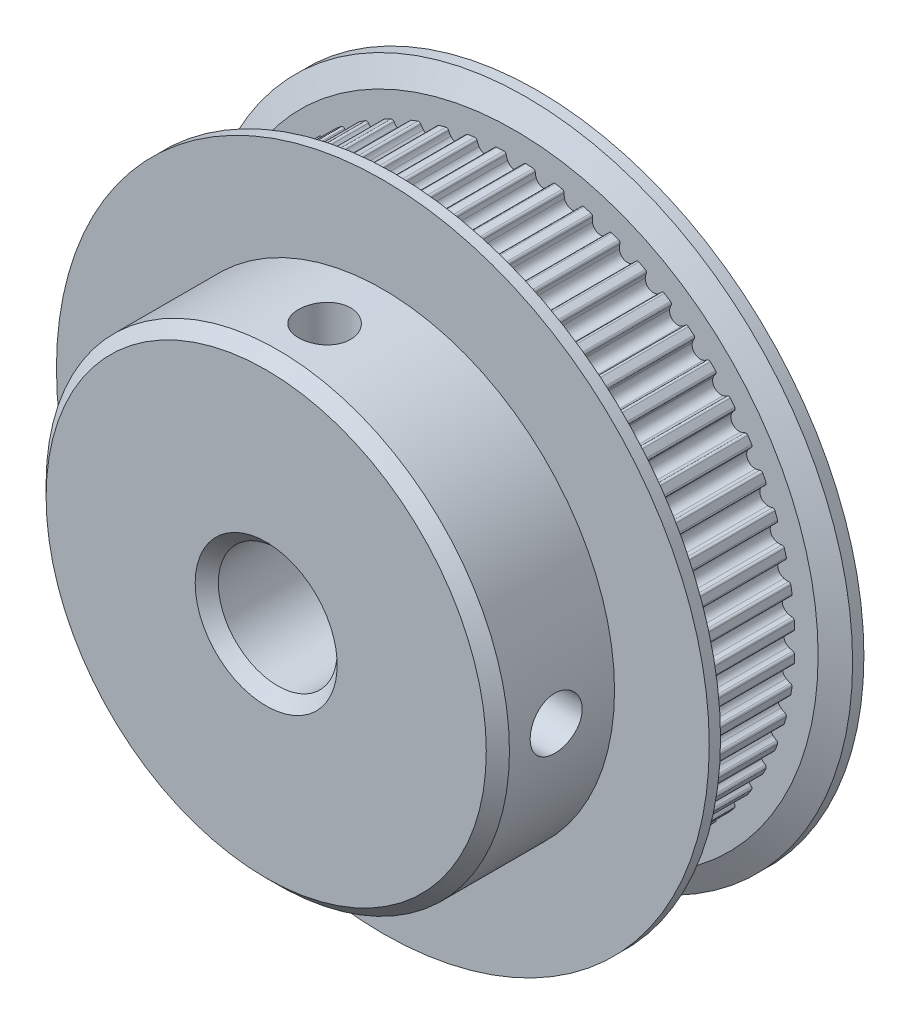
SolidWorks part; units mm, degrees
ref_plane "Front Plane" through (0, 0, 0) normal (0, 0, 1) x (1, 0, 0)
ref_plane "Top Plane" through (0, 0, 0) normal (0, 1, 0) x (1, 0, 0)
ref_plane "Right Plane" through (0, 0, 0) normal (1, 0, 0) x (0, 0, -1)
sketch "Sketch1" plane through (0, 0, 0) normal (0, 0, 1) x (1, 0, 0)
  line L1 (-1.9027, 18.097) -> (1.9027, 18.097) construction
  line L4 (0, 0) -> (0, 18.097) construction
  line L5 (0, 18.097) -> (0, 19.7034) construction
  line L6 (0, 19.101) -> (1.9973, 18.9963) construction
  line L7 (1.9973, 18.9963) -> (2.8966, 18.9017) construction
  line L8 (1.9973, 18.9963) -> (1.9027, 18.097) construction
  line L9 (-1.9973, 18.9963) -> (-1.9027, 18.097) construction
  line L10 (-1.9707, 18.7437) -> (-2.31, 21.971)
  line L11 (-2.31, 21.971) -> (2.31, 21.971)
  line L12 (2.31, 21.971) -> (1.9707, 18.7437)
  circle A0 centre (0, 0) radius 19.101 construction
  circle A1 centre (0, 0) radius 21.971 construction
  circle A2 centre (0, 0) radius 18.847 construction
  arc A3 (-0.4989, 18.4088) -> (0.4989, 18.4088) centre (0, 18.652) ccw
  arc A4 (-0.4989, 18.4088) -> (-0.5897, 18.7039) centre (0.4, 18.847) cw
  arc A5 (-1.9707, 18.7437) -> (-0.7441, 18.8323) centre (0, 0) cw
  arc A6 (-0.5897, 18.7039) -> (-0.7441, 18.8323) centre (-0.7382, 18.6824) ccw
  arc A7 (1.9707, 18.7437) -> (0.7441, 18.8323) centre (0, 0) ccw
  arc A8 (0.5897, 18.7039) -> (0.7441, 18.8323) centre (0.7382, 18.6824) cw
  arc A9 (0.4989, 18.4088) -> (0.5897, 18.7039) centre (-0.4, 18.847) ccw
  point P6 (0, 20.9083)
  point P11 (0, 19.101)
  point P13 (0, 21.971)
  point P14 (0, 18.847)
  dimension "D1" = 1.2049
  dimension "D2" = 0.6024
sketch "Sketch2" plane through (0, 0, 0) normal (1, 0, 0) x (0, 0, -1)
  line L0 (-9.1313, 4) -> (9.1313, 4)
  line L1 (-9.1313, 4) -> (-9.1313, 15.595)
  line L2 (-9.1313, 15.595) -> (-1.2787, 15.595)
  line L3 (-1.2787, 15.595) -> (-1.2787, 21.971)
  line L4 (-1.2787, 21.971) -> (0.2413, 21.971) construction
  line L5 (0.2413, 21.971) -> (0.2413, 18.847) construction
  line L6 (0.2413, 18.847) -> (7.6113, 18.847)
  line L7 (7.6113, 18.847) -> (7.6113, 21.971) construction
  line L8 (7.6113, 21.971) -> (9.1313, 21.971) construction
  line L9 (9.1313, 21.971) -> (9.1313, 4)
  line L10 (-9.1313, 0) -> (9.1313, 0) construction
  line L11 (8.3713, 21.971) -> (7.6113, 20.409)
  line L12 (0.2413, 20.409) -> (-0.5187, 21.971)
  line L13 (-1.2787, 21.971) -> (-0.5187, 21.971)
  line L14 (0.2413, 20.409) -> (0.2413, 18.847)
  line L15 (7.6113, 18.847) -> (7.6113, 20.409)
  line L16 (8.3713, 21.971) -> (9.1313, 21.971)
  arc A0 (0.2413, 20.409) -> (-0.5187, 21.971) centre (-1.7439, 20.409) ccw construction
  arc A1 (7.6113, 20.409) -> (8.3713, 21.971) centre (9.5965, 20.409) cw construction
  point P12 (0.2413, 20.409)
  point P14 (-0.5187, 21.971)
  point P20 (7.6113, 20.409)
  point P21 (8.3713, 21.971)
  point P25 (7.6113, 0)
  point P26 (0.2413, 0)
revolve "Revolve1" add sketch "Sketch2" angle 360 mid plane about L10
sketch "Sketch3" plane through (0, 0, 0) normal (0, 0, 1) x (1, 0, 0)
  line L6 (2.31, 21.971) -> (-2.31, 21.971)
  line L7 (1.9707, 18.7437) -> (2.31, 21.971)
  line L8 (-2.31, 21.971) -> (-1.9707, 18.7437)
  line L9 (2.31, 21.971) -> (-2.31, 21.971)
  line L10 (1.9707, 18.7437) -> (2.31, 21.971)
  line L11 (-2.31, 21.971) -> (-1.9707, 18.7437)
  arc A8 (1.9707, 18.7437) -> (0.7441, 18.8323) centre (0, 0) ccw
  arc A9 (0.7441, 18.8323) -> (0.5897, 18.7039) centre (0.7382, 18.6824) ccw
  arc A10 (0.4989, 18.4088) -> (0.5897, 18.7039) centre (-0.4, 18.847) ccw
  arc A11 (-0.4989, 18.4088) -> (0.4989, 18.4088) centre (0, 18.652) ccw
  arc A12 (-0.5897, 18.7039) -> (-0.4989, 18.4088) centre (0.4, 18.847) ccw
  arc A13 (-0.5897, 18.7039) -> (-0.7441, 18.8323) centre (-0.7382, 18.6824) ccw
  arc A14 (-0.7441, 18.8323) -> (-1.9707, 18.7437) centre (0, 0) ccw
  arc A15 (1.9707, 18.7437) -> (0.7441, 18.8323) centre (0, 0) ccw
  arc A16 (0.7441, 18.8323) -> (0.5897, 18.7039) centre (0.7382, 18.6824) ccw
  arc A17 (0.4989, 18.4088) -> (0.5897, 18.7039) centre (-0.4, 18.847) ccw
  arc A18 (-0.4989, 18.4088) -> (0.4989, 18.4088) centre (0, 18.652) ccw
  arc A19 (-0.5897, 18.7039) -> (-0.4989, 18.4088) centre (0.4, 18.847) ccw
  arc A20 (-0.5897, 18.7039) -> (-0.7441, 18.8323) centre (-0.7382, 18.6824) ccw
  arc A21 (-0.7441, 18.8323) -> (-1.9707, 18.7437) centre (0, 0) ccw
  dimension "D1" = 0
extrude "Cut-Extrude1" cut sketch "Sketch3" against normal up to vertex (7.6113 mm away) from vertex up to point (0, 18.847, -7.6113) starting at point (0, 18.847, -0.2413)
pattern_circular "CirPattern1" count 60 over 360 about axis through (0, 0, 9.1313) along (0, 0, 1) of "Cut-Extrude1"
sketch "Sketch4" plane through (0, 0, 0) normal (1, 0, 0) x (0, -1, 0)
  line L0 (0, -1.2787) -> (0, -9.1313) construction
  line L1 (-15.595, -1.2787) -> (15.595, -1.2787) construction
  line L2 (-15.595, -9.1313) -> (15.595, -9.1313) construction
  circle A0 centre (0, -5.205) radius 1.7526
extrude "Cut-Extrude2" cut sketch "Sketch4" along normal through all
ref_plane "Plane1" through (0, 0, 5.205) normal (0, 0, 1) x (1, 0, 0)
sketch "Sketch5" plane through (0, 0, 5.205) normal (0, 0, 1) x (1, 0, 0)
  line L0 (0, 0.1664) -> (0, 15.595) construction
  line L1 (4, -1.3716) -> (4, 0)
  line L2 (4.381, -1.7526) -> (15.1152, -1.7526)
  line L3 (4, 0) -> (15.595, 0) construction
  line L4 (4, 0) -> (15.4962, 0)
  line L5 (15.4962, 0) -> (15.4962, -1.3716)
  line L6 (4.381, -1.7526) -> (4, -1.3716)
  line L7 (15.4962, -1.3716) -> (15.1152, -1.7526)
  circle A0 centre (0, 0) radius 15.595 construction
  circle A1 centre (0, 0) radius 4 construction
  point P2 (4, -1.7526)
  point P11 (15.4962, -1.7526)
revolve "Revolve2" [suppressed] add sketch "Sketch5" angle 360 mid plane about L4
sketch "Sketch6" [suppressed] plane through (15.4207, 5.3841, 0) normal (-1, 0, 0) x (0, -1, 0)
  line L1 (5.3841, 6.2169) -> (4.5078, 5.7109)
  line L2 (4.5078, 5.7109) -> (4.5078, 4.6991)
  line L3 (4.5078, 4.6991) -> (5.3841, 4.1931)
  line L4 (5.3841, 4.1931) -> (6.2604, 4.6991)
  line L5 (6.2604, 4.6991) -> (6.2604, 5.7109)
  line L6 (6.2604, 5.7109) -> (5.3841, 6.2169)
  circle A0 centre (5.3841, 5.205) radius 0.8763 construction
  dimension "D1" = 1.7526
extrude "Cut-Extrude3" [suppressed] cut sketch "Sketch6" along normal blind 1.3144
pattern_circular "CirPattern2" count 2 every 90 about axis through (0, 0, 9.1313) along (0, 0, 1) of "Cut-Extrude2", "Revolve2", "Cut-Extrude3"
chamfer "Chamfer1" distance 0.7798 angle 45 2 edges at (4, 0, 9.1313) (15.595, 0, 9.1313)
ref_axis "Center Axis 1" through (0, 0, -9.1313) along (0, 0, 1)
ref_plane "Contact Plane 1" through (0, 0, 9.1313) normal (0, 0, 1) x (1, 0, 0)
ref_plane "Contact Plane 2" through (0, 0, -9.1313) normal (0, 0, -1) x (-1, 0, 0)
sketch "Sketch7" plane through (0, 0, 9.1313) normal (0, 0, 1) x (1, 0, 0)
  circle A0 centre (0, 0) radius 4.175
  dimension "D1" = 8.35
equation "\"D2@Sketch1\" = \"D1@Sketch1\"/2"
equation "\"D1@Sketch6\" = \"Set Screw@Sketch4\" / 2"
equation "\"D1@Cut-Extrude3\" = \"D1@Sketch6\"*.75"
equation "\"D1@Chamfer1\"=\"Hub Dia@Sketch2\"*.025"
